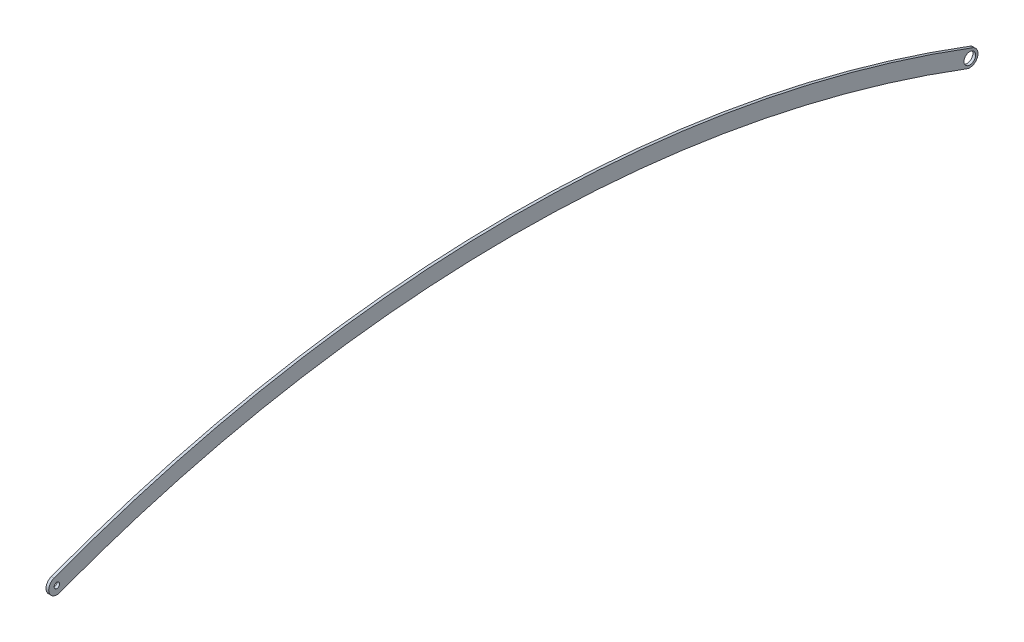
SolidWorks part; units mm, degrees
material "ASTM A36 Steel"
ref_plane "Front Plane" through (0, 0, 0) normal (0, 0, 1) x (1, 0, 0)
ref_plane "Top Plane" through (0, 0, 0) normal (0, 1, 0) x (1, 0, 0)
ref_plane "Right Plane" through (0, 0, 0) normal (1, 0, 0) x (0, 0, -1)
sketch "Sketch1" plane through (0, 0, 0) normal (1, 0, 0) x (0, 0, -1)
  line L0 (0, 0) -> (530.0811, 0) construction
  arc A6 (0, 0) -> (530.0811, 0) centre (265.0405, -700.8595) cw construction
  circle A7 centre (0, 0) radius 1.6
  circle A8 centre (0, 0) radius 4.7625
  circle A11 centre (530.0811, 0) radius 3.3782
  circle A12 centre (530.0811, 0) radius 4.7625
  arc A13 (-1.6846, 4.4546) -> (531.7657, 4.4546) centre (265.0405, -700.8595) cw
  arc A14 (1.6846, -4.4546) -> (528.3965, -4.4546) centre (265.0405, -700.8595) cw
  point P13 (0, 0)
  point P14 (-1.8716, 4.3793)
  point P15 (531.3295, 4.596)
  point P16 (527.8563, -8.1841)
  dimension "D4" = 6.7564
  dimension "D1" = 530.0811
  dimension "D2" = 749.3
  dimension "D3" = 3.2
  dimension "D5" = 9.525
  dimension "D6" = 9.525
extrude "Boss-Extrude1" add sketch "Sketch1" along normal blind 1.5875 contours A8 A7 | A8 A14 A12 A13 | A12 A11 region at (0, -2.6307, -3.8074) region at (0, 4.3596, -3.0123) region at (0, 2.6307, -533.8885)
ref_point "Point2"
sketch "Sketch3" plane through (1.5875, 0, 0) normal (1, 0, 0) x (0, 0, -1)
  line L0 (518.2753, 9.5562) -> (531.7657, 4.4546) construction
  line L1 (530.0811, 0) -> (523.6697, 2.4246) construction
  line L2 (530.0811, 0) -> (528.728, -6.5887) construction
  line L3 (530.0811, 0) -> (539.6967, -1.9746) construction
  arc A0 (528.3965, -4.4546) -> (531.7657, 4.4546) centre (530.0811, 0) ccw construction
  dimension "D1" = 99.11
